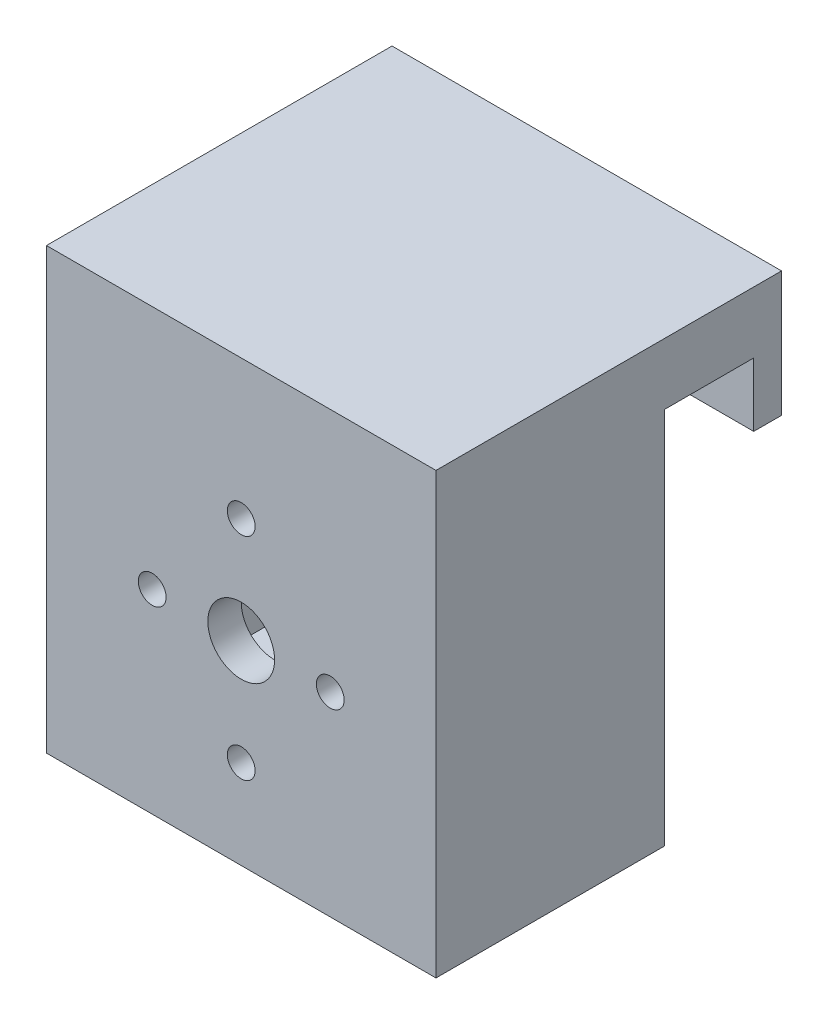
SolidWorks part; units mm, degrees
note: The reader was unsure of these and kept them because the rebuilt part matched: shared geometry of "Sketch2<2>", "Sketch4<3>".
material "ABS"
ref_plane "Front Plane" through (0, 0, 0) normal (0, 0, 1) x (1, 0, 0)
ref_plane "Top Plane" through (0, 0, 0) normal (0, 1, 0) x (1, 0, 0)
ref_plane "Right Plane" through (0, 0, 0) normal (1, 0, 0) x (0, 0, -1)
sketch "Sketch1" plane through (0, 0, 0) normal (0, 0, 1) x (1, 0, 0)
  line L8 (-10.8807, -4.941) -> (-10.6773, -4.7376)
  line L9 (-4.7376, -10.6773) -> (-4.941, -10.8807)
  line L10 (4.941, -10.8807) -> (4.7376, -10.6773)
  line L11 (10.6773, -4.7376) -> (10.8807, -4.941)
  line L12 (10.8807, 4.941) -> (10.6773, 4.7376)
  line L13 (4.7376, 10.6773) -> (4.941, 10.8807)
  line L14 (-4.941, 10.8807) -> (-4.7376, 10.6773)
  line L15 (-10.6773, 4.7376) -> (-10.8807, 4.941)
  line L16 (-10.8807, -4.941) -> (-10.6773, -4.7376)
  line L17 (-4.7376, -10.6773) -> (-4.941, -10.8807)
  line L18 (4.941, -10.8807) -> (4.7376, -10.6773)
  line L19 (10.6773, -4.7376) -> (10.8807, -4.941)
  line L20 (10.8807, 4.941) -> (10.6773, 4.7376)
  line L21 (4.7376, 10.6773) -> (4.941, 10.8807)
  line L22 (-4.941, 10.8807) -> (-4.7376, 10.6773)
  line L23 (-10.6773, 4.7376) -> (-10.8807, 4.941)
  circle A0 centre (8, 0) radius 1.25 construction
  circle A1 centre (8, 0) radius 1.25
  circle A2 centre (0, 9.5) radius 1.25 construction
  circle A3 centre (0, 9.5) radius 1.25
  circle A4 centre (0, -9.5) radius 1.25 construction
  circle A5 centre (0, -9.5) radius 1.25
  circle A6 centre (-8, 0) radius 1.25 construction
  circle A7 centre (-8, 0) radius 1.25
  arc A8 (-10.8807, 4.941) -> (-10.8807, -4.941) centre (0, 0) ccw
  arc A9 (-4.7376, -10.6773) -> (-10.6773, -4.7376) centre (-7.7075, -7.7075) ccw
  arc A10 (-4.941, -10.8807) -> (4.941, -10.8807) centre (0, 0) ccw
  arc A11 (10.6773, -4.7376) -> (4.7376, -10.6773) centre (7.7075, -7.7075) ccw
  arc A12 (10.8807, -4.941) -> (10.8807, 4.941) centre (0, 0) ccw
  arc A13 (4.7376, 10.6773) -> (10.6773, 4.7376) centre (7.7075, 7.7075) ccw
  arc A14 (4.941, 10.8807) -> (-4.941, 10.8807) centre (0, 0) ccw
  arc A15 (-10.6773, 4.7376) -> (-4.7376, 10.6773) centre (-7.7075, 7.7075) ccw
  arc A16 (-10.8807, 4.941) -> (-10.8807, -4.941) centre (0, 0) ccw
  arc A17 (-4.7376, -10.6773) -> (-10.6773, -4.7376) centre (-7.7075, -7.7075) ccw
  arc A18 (-4.941, -10.8807) -> (4.941, -10.8807) centre (0, 0) ccw
  arc A19 (10.6773, -4.7376) -> (4.7376, -10.6773) centre (7.7075, -7.7075) ccw
  arc A20 (10.8807, -4.941) -> (10.8807, 4.941) centre (0, 0) ccw
  arc A21 (4.7376, 10.6773) -> (10.6773, 4.7376) centre (7.7075, 7.7075) ccw
  arc A22 (4.941, 10.8807) -> (-4.941, 10.8807) centre (0, 0) ccw
  arc A23 (-10.6773, 4.7376) -> (-4.7376, 10.6773) centre (-7.7075, 7.7075) ccw
  circle A24 centre (0, 0) radius 3
  dimension "D1" = 0
extrude "Boss-Extrude1" add sketch "Sketch1" along normal blind 3
sketch "Sketch2" plane through (0, 0, 3) normal (0, 0, 1) x (1, 0, 0)
  line L1 (15, 15) -> (-15, 15)
  line L2 (15, 15) -> (15, -15)
  line L3 (15, -15) -> (-15, -15)
  line L4 (-15, 15) -> (-15, -15)
  line L5 (15, 15) -> (-15, -15) construction
  line L6 (15, -15) -> (-15, 15) construction
  line L8 (17.5, 22) -> (17.5, -17.5)
  line L9 (17.5, -17.5) -> (-17.5, -17.5)
  line L10 (-17.5, 22) -> (-17.5, -17.5)
  line L11 (17.5, 17.5) -> (-17.5, -17.5) construction
  line L12 (17.5, -17.5) -> (-17.5, 17.5) construction
  line L13 (17.5, 22) -> (-17.5, 22)
  circle A0 centre (0, 0) radius 13.95 construction
  circle A1 centre (0, 0) radius 13.95 construction
  point P0 (0, 0)
  arc M11 (-10.8807, 4.941) -> (-10.8807, -4.941) centre (0, 0) ccw
  line M12 (-10.8807, -4.941) -> (-10.6773, -4.7376)
  arc M13 (-10.6773, -4.7376) -> (-4.7376, -10.6773) centre (-7.7075, -7.7075) cw
  line M14 (-4.7376, -10.6773) -> (-4.941, -10.8807)
  arc M15 (-4.941, -10.8807) -> (4.941, -10.8807) centre (0, 0) ccw
  line M16 (4.941, -10.8807) -> (4.7376, -10.6773)
  arc M17 (4.7376, -10.6773) -> (10.6773, -4.7376) centre (7.7075, -7.7075) cw
  line M18 (10.6773, -4.7376) -> (10.8807, -4.941)
  arc M19 (10.8807, -4.941) -> (10.8807, 4.941) centre (0, 0) ccw
  line M20 (10.8807, 4.941) -> (10.6773, 4.7376)
  arc M21 (10.6773, 4.7376) -> (4.7376, 10.6773) centre (7.7075, 7.7075) cw
  line M22 (4.7376, 10.6773) -> (4.941, 10.8807)
  arc M23 (4.941, 10.8807) -> (-4.941, 10.8807) centre (0, 0) ccw
  line M24 (-4.941, 10.8807) -> (-4.7376, 10.6773)
  arc M25 (-4.7376, 10.6773) -> (-10.6773, 4.7376) centre (-7.7075, 7.7075) cw
  line M26 (-10.6773, 4.7376) -> (-10.8807, 4.941)
  dimension "D1" = 15
  dimension "D3" = 27.9
  dimension "D2" = 2.5
  dimension "D4" = 7
extrude "Boss-Extrude2" add sketch "Sketch2" against normal blind 20.55 separate body
extrude "Boss-Extrude3" add sketch "Sketch2<2>" against normal blind 3 contours L1 L4 L3 L2 M11 M26 M25 M24 M23 M22 M21 M20 M19 M18 M17 M16 M15 M14 M13 M12
sketch "Sketch2<2>" plane through (0, 0, 3) normal (0, 0, 1) x (1, 0, 0) same geometry as "Sketch2"
ref_plane "Plane1" through (0, 0, -17.55) normal (0, 0, -1) x (-1, 0, 0)
sketch "Sketch3" plane through (0, 0, -17.55) normal (0, 0, -1) x (-1, 0, 0)
  line L2 (15, 15) -> (15, -15) construction
  line L3 (-15, -15) -> (-15, 15) construction
  line L4 (-17.5, -17.5) -> (-17.5, 22) construction
  line L5 (17.5, 10.7577) -> (-17.5, 10.7577)
  line L6 (17.5, 22) -> (17.5, -17.5) construction
  line L7 (15, 15) -> (15, -15) construction
  line L8 (-15, -15) -> (-15, 15) construction
  line L9 (-17.5, -17.5) -> (-17.5, 22) construction
  line L10 (17.5, 22) -> (17.5, -17.5) construction
  line L11 (-17.5, 10.7577) -> (-17.5, 22)
  line L13 (-17.5, 22) -> (17.5, 22) construction
  line L15 (17.5, 22) -> (17.5, 10.7577)
  line L16 (-17.5, 22) -> (17.5, 22)
extrude "Boss-Extrude4" add sketch "Sketch3" along normal blind 10.5
sketch "Sketch4" plane through (17.5, 0, 0) normal (1, 0, 0) x (0, 0, -1)
  line L0 (17.55, 9.725) -> (17.55, 15.975) construction
  line L1 (17.55, 10.7577) -> (17.55, 16.475)
  line L2 (25.55, 9.725) -> (25.55, 15.975) construction
  line L3 (25.55, 10.7577) -> (25.55, 16.475)
  line L5 (25.55, 10.7577) -> (25.55, 15.975)
  line L6 (-3, 22) -> (-3, -17.5)
  line L7 (-3, -17.5) -> (17.55, -17.5)
  line L8 (17.55, -17.5) -> (17.55, 10.7577)
  line L9 (17.55, 10.7577) -> (28.05, 10.7577)
  line L10 (28.05, 10.7577) -> (28.05, 22)
  line L11 (21.55, 20.1108) -> (21.55, 11.8392) construction
  line L12 (-3, 22) -> (-3, -17.5)
  line L13 (-3, -17.5) -> (17.55, -17.5)
  line L14 (17.55, -17.5) -> (17.55, 10.7577)
  line L15 (17.55, 10.7577) -> (28.05, 10.7577)
  line L16 (28.05, 10.7577) -> (28.05, 22)
  line L17 (23.8, 16.975) -> (23.8, 16.475)
  line L19 (17.55, 10.7577) -> (17.55, 15.975)
  line L20 (17.55, 16.475) -> (25.55, 16.475)
  line L21 (19.3, 16.975) -> (19.3, 16.475)
  line L22 (21.8202, 17.175) -> (21.2798, 17.175)
  line L27 (17.55, 9.725) -> (25.55, 9.725)
  line L28 (28.05, 22) -> (-3, 22)
  line L29 (28.05, 22) -> (-3, 22)
  line L30 (25.55, 9.725) -> (25.55, 15.975)
  line L31 (25.55, 15.975) -> (17.55, 15.975)
  line L32 (17.55, 15.975) -> (17.55, 9.725)
  line L33 (17.55, 9.725) -> (25.55, 9.725)
  line L34 (25.55, 9.725) -> (25.55, 15.975)
  line L35 (25.55, 15.975) -> (17.55, 15.975) construction
  line L36 (17.55, 15.975) -> (17.55, 9.725)
  arc A0 (21.2798, 17.175) -> (19.3, 16.975) centre (20.3, 16.975) ccw
  arc A1 (23.8, 16.975) -> (21.8202, 17.175) centre (22.8, 16.975) ccw
  point P15 (21.55, 15.975)
  point P18 (23.4533, 15.975)
  point P26 (17.8717, 17.047)
  dimension "D4" = 2
  dimension "D2" = 0.5
  dimension "D6" = 0
  dimension "D3" = 2.5
  dimension "D5" = 0.2
  dimension "D7" = 0.5
  dimension "D1" = 0
extrude "Cut-Extrude1" cut sketch "Sketch4" against normal up to next
extrude "Cut-Extrude2" cut sketch "Sketch4<3>" against normal offset from surface (31 mm away) 2 from offset 2
sketch "Sketch4<3>" plane through (17.5, 0, 0) normal (1, 0, 0) x (0, 0, -1) same geometry as "Sketch4"
